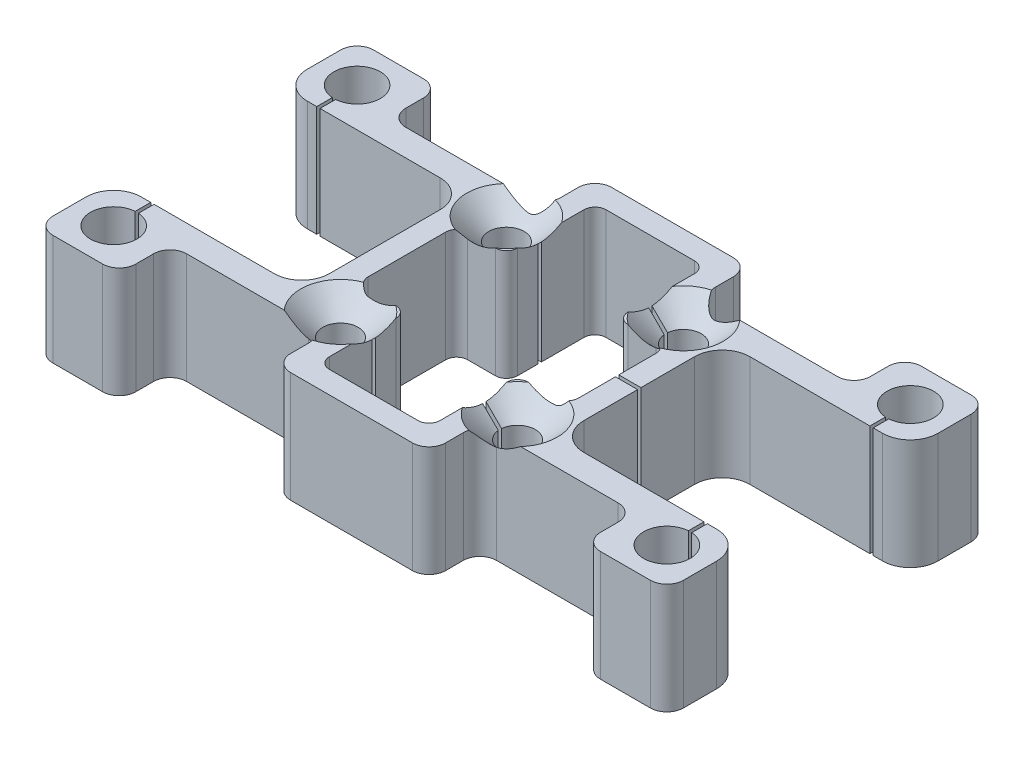
SolidWorks part; units mm, degrees
material "6061 合金"
ref_plane "前视基准面" through (0, 0, 0) normal (0, 0, 1) x (1, 0, 0)
ref_plane "上视基准面" through (0, 0, 0) normal (0, 1, 0) x (1, 0, 0)
ref_plane "右视基准面" through (0, 0, 0) normal (1, 0, 0) x (0, 0, -1)
sketch "草图1" plane through (0, 0, 0) normal (0, 1, 0) x (1, 0, 0)
  line L1 (-28.5, 14.5) -> (28.5, 14.5)
  line L2 (-28.5, 14.5) -> (-28.5, -14.5)
  line L3 (-28.5, -14.5) -> (28.5, -14.5)
  line L4 (28.5, 14.5) -> (28.5, -14.5)
  line L5 (-28.5, 14.5) -> (28.5, -14.5) construction
  line L6 (-28.5, -14.5) -> (28.5, 14.5) construction
  line L7 (-25, 11) -> (25, 11) construction
  line L8 (-25, 11) -> (-25, -11) construction
  line L9 (-25, -11) -> (25, -11) construction
  line L10 (25, 11) -> (25, -11) construction
  line L11 (-25, 11) -> (25, -11) construction
  line L12 (-25, -11) -> (25, 11) construction
  circle A0 centre (-25, 11) radius 2.1
  circle A1 centre (-25, -11) radius 2.1
  circle A2 centre (25, 11) radius 2.1
  circle A3 centre (25, -11) radius 2.1
  point P0 (0, 0)
  point P5 (0, 0)
  dimension "D1" = 4.2
  dimension "D4" = 3.5
  dimension "D5" = 3.5
  dimension "D2" = 50
  dimension "D3" = 22
extrude "凸台-拉伸1" add sketch "草图1" along normal blind 10
fillet "圆角1" radius 1.5 4 edges at (-28.5, 5, -14.5) (-28.5, 5, 14.5) (28.5, 5, -14.5) (28.5, 5, 14.5)
sketch "草图2" plane through (0, 10, 0) normal (0, 1, 0) x (1, 0, 0)
  line L1 (-8, 7.5) -> (8, 7.5) construction
  line L2 (-8, 7.5) -> (-8, -7.5) construction
  line L3 (-8, -7.5) -> (8, -7.5) construction
  line L4 (8, 7.5) -> (8, -7.5) construction
  line L5 (-8, 7.5) -> (8, -7.5) construction
  line L6 (-8, -7.5) -> (8, 7.5) construction
  circle A0 centre (8, 7.5) radius 1.6
  circle A1 centre (-8, 7.5) radius 1.6
  circle A2 centre (-8, -7.5) radius 1.6
  circle A3 centre (8, -7.5) radius 1.6
  point P0 (0, 0)
  dimension "D1" = 3.2
  dimension "D2" = 16
  dimension "D3" = 15
extrude "切除-拉伸1" cut sketch "草图2" against normal blind 10
sketch "草图3" plane through (0, 10, 0) normal (0, 1, 0) x (1, 0, 0)
  line L0 (0, 0) -> (28.5, 0) construction
  line L1 (28.5, -13) -> (28.5, 13) construction
  line L2 (0, 0) -> (0, 14.5) construction
  line L3 (28.5, -7.5) -> (11.5, -7.5)
  line L4 (28.5, -7.5) -> (28.5, 7.5)
  line L5 (28.5, 7.5) -> (11.5, 7.5)
  line L6 (11.5, -7.5) -> (11.5, 7.5)
  line L7 (27, 14.5) -> (-27, 14.5) construction
  line L8 (-28.5, 7.5) -> (-11.5, 7.5)
  line L9 (-11.5, -7.5) -> (-11.5, 7.5)
  line L10 (-28.5, -7.5) -> (-11.5, -7.5)
  line L11 (-28.5, -7.5) -> (-28.5, 7.5)
  circle A0 centre (25, 11) radius 2.1 construction
  dimension "D1" = 3.5
  dimension "D2" = 17
extrude "切除-拉伸2" cut sketch "草图3" against normal blind 10
fillet "圆角2" radius 2.5 8 edges at (-28.5, 5, -7.5) (-28.5, 5, 7.5) (-11.5, 5, 7.5) (-11.5, 5, -7.5) (28.5, 5, 7.5) (11.5, 5, 7.5) (11.5, 5, -7.5) (28.5, 5, -7.5)
chamfer "倒角1" distance 2 angle 45 4 edges at (8, 10, -5.9) (8, 10, 9.1) (-8, 10, 9.1) (-8, 10, -5.9)
sketch "草图4" plane through (0, 0, 0) normal (0, -1, 0) x (1, 0, 0)
  line L0 (0, 14.5) -> (0, 0) construction
  line L1 (-27, 14.5) -> (27, 14.5) construction
  line L2 (0, 0) -> (11.5, 0) construction
  line L3 (11.5, -5) -> (11.5, 5) construction
  line L4 (-5, 12.5) -> (5, 12.5)
  line L5 (5, 12.5) -> (5, 4.5)
  line L6 (5, 4.5) -> (9.5, 4.5)
  line L7 (9.5, 4.5) -> (9.5, -4.5)
  line L8 (9.5, -4.5) -> (5, -4.5)
  line L9 (5, -4.5) -> (5, -12.5)
  line L10 (5, -12.5) -> (-5, -12.5)
  line L11 (-5, -4.5) -> (-5, -12.5)
  line L12 (-9.5, -4.5) -> (-5, -4.5)
  line L13 (-9.5, 4.5) -> (-9.5, -4.5)
  line L14 (-5, 4.5) -> (-9.5, 4.5)
  line L15 (-5, 12.5) -> (-5, 4.5)
  circle A0 centre (8, 7.5) radius 1.6 construction
  point P17 (0, -12.5)
  point P22 (0, 12.5)
  dimension "D1" = 3
  dimension "D2" = 3
  dimension "D3" = 2
  dimension "D4" = 2
extrude "切除-拉伸3" cut sketch "草图4" against normal blind 10
fillet "圆角3" radius 1 12 edges at (-5, 5, 4.5) (-9.5, 4.8771, 4.5) (-9.5, 4.8771, -4.5) (-5, 5, -4.5) (-5, 5, -12.5) (5, 5, -12.5) (5, 5, -4.5) (9.5, 4.8771, -4.5) (9.5, 4.8771, 4.5) (5, 5, 4.5) (5, 5, 12.5) (-5, 5, 12.5)
sketch "草图5" plane through (0, 0, 0) normal (0, -1, 0) x (1, 0, 0)
  line L0 (9.5, 0) -> (11.5, 0) construction
  line L3 (9.5, -3.5) -> (9.5, 3.5) construction
  line L8 (11.5, -5) -> (11.5, 5) construction
  line L10 (8.3913, 0.15) -> (12.6087, 0.15)
  line L11 (8.3913, 0.15) -> (8.3913, -0.15)
  line L12 (8.3913, -0.15) -> (12.6087, -0.15)
  line L13 (12.6087, 0.15) -> (12.6087, -0.15)
  line L14 (8.3913, 0.15) -> (12.6087, -0.15) construction
  line L15 (8.3913, -0.15) -> (12.6087, 0.15) construction
  point P6 (10.5, 0)
  dimension "D1" = 0.3
extrude "切除-拉伸5" cut sketch "草图5" against normal blind 10
sketch "草图6" plane through (0, 0, 0) normal (0, -1, 0) x (1, 0, 0)
  line L0 (0, 14.5) -> (0, 0) construction
  line L1 (-27, 14.5) -> (27, 14.5) construction
  line L2 (0, 0) -> (38.6099, 0) construction
  line L3 (5, 5.5) -> (5, 11.5) construction
  line L4 (7, 14.5) -> (21, 14.5)
  line L5 (7, 14.5) -> (7, 9.9)
  line L6 (7, 9.9) -> (21, 9.9)
  line L7 (21, 14.5) -> (21, 9.9)
  line L8 (21, -14.5) -> (21, -9.9)
  line L9 (7, -9.9) -> (21, -9.9)
  line L10 (7, -14.5) -> (7, -9.9)
  line L11 (7, -14.5) -> (21, -14.5)
  line L12 (-7, -14.5) -> (-21, -14.5)
  line L13 (-7, -14.5) -> (-7, -9.9)
  line L14 (-7, -9.9) -> (-21, -9.9)
  line L15 (-21, -14.5) -> (-21, -9.9)
  line L16 (-21, 14.5) -> (-21, 9.9)
  line L17 (-7, 9.9) -> (-21, 9.9)
  line L18 (-7, 14.5) -> (-7, 9.9)
  line L19 (-7, 14.5) -> (-21, 14.5)
  dimension "D1" = 4.6
  dimension "D2" = 2
  dimension "D3" = 14
extrude "切除-拉伸6" cut sketch "草图6" against normal blind 10
fillet "圆角4" radius 1.5 16 edges at (-21, 5, -14.5) (-21, 5, -9.9) (-7, 4.5, -9.9) (-7, 5, -14.5) (7, 5, -14.5) (7, 4.5, -9.9) (21, 5, -9.9) (21, 5, -14.5) (21, 5, 14.5) (7, 5, 14.5) (7, 4.5, 9.9) (21, 5, 9.9) (-7, 5, 14.5) (-7, 4.5, 9.9) (-21, 5, 9.9) (-21, 5, 14.5)
sketch "草图7" plane through (0, 10, 0) normal (0, 1, 0) x (1, 0, 0)
  line L0 (0, 12.5) -> (0, 0) construction
  line L1 (-4, 12.5) -> (4, 12.5) construction
  line L2 (0, 0) -> (40.7629, 0) construction
  line L3 (25, 11) -> (25, 7.5) construction
  line L4 (26, 7.5) -> (14, 7.5) construction
  line L5 (24.85, -6.9591) -> (25.15, -6.9591)
  line L6 (24.85, 11.5409) -> (25.15, 11.5409)
  line L7 (24.85, 11.5409) -> (24.85, 6.9591)
  line L8 (24.85, 6.9591) -> (25.15, 6.9591)
  line L9 (25.15, 11.5409) -> (25.15, 6.9591)
  line L10 (24.85, 11.5409) -> (25.15, 6.9591) construction
  line L11 (24.85, 6.9591) -> (25.15, 11.5409) construction
  line L12 (25.15, -11.5409) -> (25.15, -6.9591)
  line L13 (24.85, -11.5409) -> (25.15, -11.5409)
  line L14 (24.85, -11.5409) -> (24.85, -6.9591)
  line L15 (-24.85, -11.5409) -> (-24.85, -6.9591)
  line L16 (-24.85, -11.5409) -> (-25.15, -11.5409)
  line L17 (-25.15, -11.5409) -> (-25.15, -6.9591)
  line L18 (-24.85, -6.9591) -> (-25.15, -6.9591)
  line L19 (-24.85, 6.9591) -> (-25.15, 11.5409) construction
  line L20 (-24.85, 11.5409) -> (-25.15, 6.9591) construction
  line L21 (-25, 11) -> (-25, 7.5) construction
  line L22 (-25.15, 11.5409) -> (-25.15, 6.9591)
  line L23 (-24.85, 6.9591) -> (-25.15, 6.9591)
  line L24 (-24.85, 11.5409) -> (-24.85, 6.9591)
  line L25 (-24.85, 11.5409) -> (-25.15, 11.5409)
  point P11 (25, 9.25)
  point P30 (-25, 9.25)
  dimension "D1" = 0.3
extrude "切除-拉伸7" cut sketch "草图7" against normal blind 10
sketch "草图8" plane through (0, 0, 0) normal (0, -1, 0) x (1, 0, 0)
  line L0 (0, 12.5) -> (0, 0) construction
  line L1 (4, 12.5) -> (-4, 12.5) construction
  line L2 (0, 0) -> (-9.5, 0) construction
  line L3 (-9.5, 3.5) -> (-9.5, -3.5) construction
  line L4 (-8, 7.5) -> (-5, 7.5) construction
  line L5 (-5, 11.5) -> (-5, 5.5) construction
  line L6 (-8.4294, -7.35) -> (-4.5706, -7.35)
  line L7 (-8.4294, 7.65) -> (-4.5706, 7.65)
  line L8 (-8.4294, 7.65) -> (-8.4294, 7.35)
  line L9 (-8.4294, 7.35) -> (-4.5706, 7.35)
  line L10 (-4.5706, 7.65) -> (-4.5706, 7.35)
  line L11 (-8.4294, 7.65) -> (-4.5706, 7.35) construction
  line L12 (-8.4294, 7.35) -> (-4.5706, 7.65) construction
  line L13 (-4.5706, -7.65) -> (-4.5706, -7.35)
  line L14 (-8.4294, -7.65) -> (-4.5706, -7.65)
  line L15 (-8.4294, -7.65) -> (-8.4294, -7.35)
  line L16 (8.4294, -7.65) -> (8.4294, -7.35)
  line L17 (8.4294, -7.65) -> (4.5706, -7.65)
  line L18 (4.5706, -7.65) -> (4.5706, -7.35)
  line L19 (8.4294, -7.35) -> (4.5706, -7.35)
  line L20 (8.4294, 7.35) -> (4.5706, 7.65) construction
  line L21 (8.4294, 7.65) -> (4.5706, 7.35) construction
  line L22 (8, 7.5) -> (5, 7.5) construction
  line L23 (4.5706, 7.65) -> (4.5706, 7.35)
  line L24 (8.4294, 7.35) -> (4.5706, 7.35)
  line L25 (8.4294, 7.65) -> (8.4294, 7.35)
  line L26 (8.4294, 7.65) -> (4.5706, 7.65)
  point P13 (-6.5, 7.5)
  point P32 (6.5, 7.5)
  dimension "D1" = 0.3
extrude "切除-拉伸8" cut sketch "草图8" against normal blind 10
